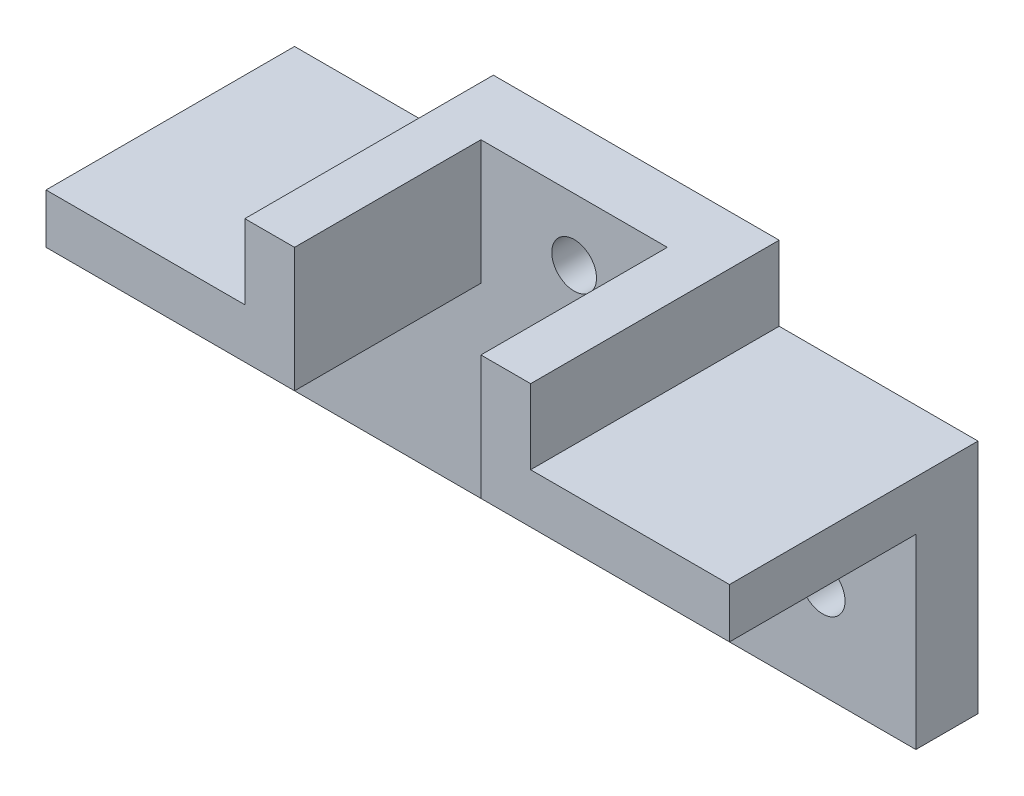
SolidWorks part; units mm, degrees
ref_plane "Front Plane" through (0, 0, 0) normal (0, 0, 1) x (1, 0, 0)
ref_plane "Top Plane" through (0, 0, 0) normal (0, 1, 0) x (1, 0, 0)
ref_plane "Right Plane" through (0, 0, 0) normal (1, 0, 0) x (0, 0, -1)
sketch "Sketch1" plane through (0, 0, 0) normal (0, 0, 1) x (1, 0, 0)
  line L0 (14.3137, 5.7353) -> (34.3137, 5.7353)
  line L1 (-20.6863, 5.7353) -> (-0.6863, 5.7353)
  line L2 (-20.6863, 5.7353) -> (-20.6863, -9.2647)
  line L3 (-20.6863, -9.2647) -> (34.3137, -9.2647)
  line L4 (34.3137, 5.7353) -> (34.3137, -9.2647)
  line L5 (-0.6863, 15.7353) -> (14.3137, 15.7353)
  line L6 (-0.6863, 15.7353) -> (-0.6863, 5.7353)
  line L8 (14.3137, 15.7353) -> (14.3137, 5.7353)
  dimension "D1" = 15
  dimension "D2" = 10
  dimension "D3" = 20
  dimension "D4" = 15
  dimension "D5" = 20
extrude "Boss-Extrude1" add sketch "Sketch1" along normal blind 5
sketch "Sketch2" plane through (0, 0, 0) normal (0, 0, -1) x (-1, 0, 0)
  line L0 (0.6863, 15.7353) -> (4.6863, 15.7353)
  line L1 (4.6863, 15.7353) -> (4.6863, 9.7353)
  line L2 (20.6863, 5.7353) -> (20.6863, 9.7353)
  line L3 (20.6863, 9.7353) -> (6.08, 9.7353)
  line L4 (20.6863, 5.7353) -> (0.6863, 5.7353)
  line L5 (0.6863, 15.7353) -> (0.6863, 5.7353)
  line L6 (6.08, 9.7353) -> (4.6863, 9.7353)
  dimension "D1" = 4
  dimension "D2" = 4
extrude "Boss-Extrude2" add sketch "Sketch2" against normal blind 20 contours L3 L6 L1 L0 L5 L4 L2
sketch "Sketch4" plane through (0, 0, 0) normal (0, 0, -1) x (-1, 0, 0)
  line L0 (20.6863, -9.2647) -> (-34.3137, -9.2647)
  line L1 (-34.3137, -9.2647) -> (-34.3137, -13.2647)
  line L2 (-34.3137, -13.2647) -> (20.6863, -13.2647)
  line L3 (20.6863, -13.2647) -> (20.6863, -9.2647)
  dimension "D1" = 4
ref_plane "Plane4" through (6.8137, 0, 0) normal (-1, 0, 0) x (0, 0, 1)
ref_plane "Plane5" through (-5.6863, 0, 0) normal (-1, 0, 0) x (0, 0, 1)
mirror "Mirror1" about plane through (6.8137, 0, 0) normal (-1, 0, 0) of "Boss-Extrude2"
sketch "Sketch6" plane through (0, 0, 5) normal (0, 0, 1) x (1, 0, 0)
  line L0 (6.8137, 3.3) -> (6.8137, -3.3) construction
  line L1 (-20.6863, 5.7353) -> (-20.6863, -9.2647) construction
  line L2 (-20.6863, 5.7353) -> (-0.6863, 5.7353) construction
  line L3 (34.3137, 5.7353) -> (14.3137, 5.7353) construction
  line L5 (34.3137, -9.2647) -> (34.3137, 5.7353) construction
  line L6 (14.3137, 15.7353) -> (-0.6863, 15.7353) construction
  circle A0 centre (6.8137, 10.7353) radius 1.8
  circle A1 centre (-13.1863, -1.7647) radius 1.8
  circle A2 centre (26.8137, -1.7647) radius 1.8
  dimension "D1" = 3.6
  dimension "D2" = 3.6
  dimension "D3" = 3.6
  dimension "D5" = 7.5
  dimension "D7" = 7.5
  dimension "D8" = 5
  dimension "D4" = 7.5
  dimension "D6" = 7.5
ref_plane "Plane6" through (-4.6863, 9.7353, 20) normal (0, -1, 0) x (-1, 0, 0)
extrude "Cut-Extrude3" cut sketch "Sketch6" against normal through all
